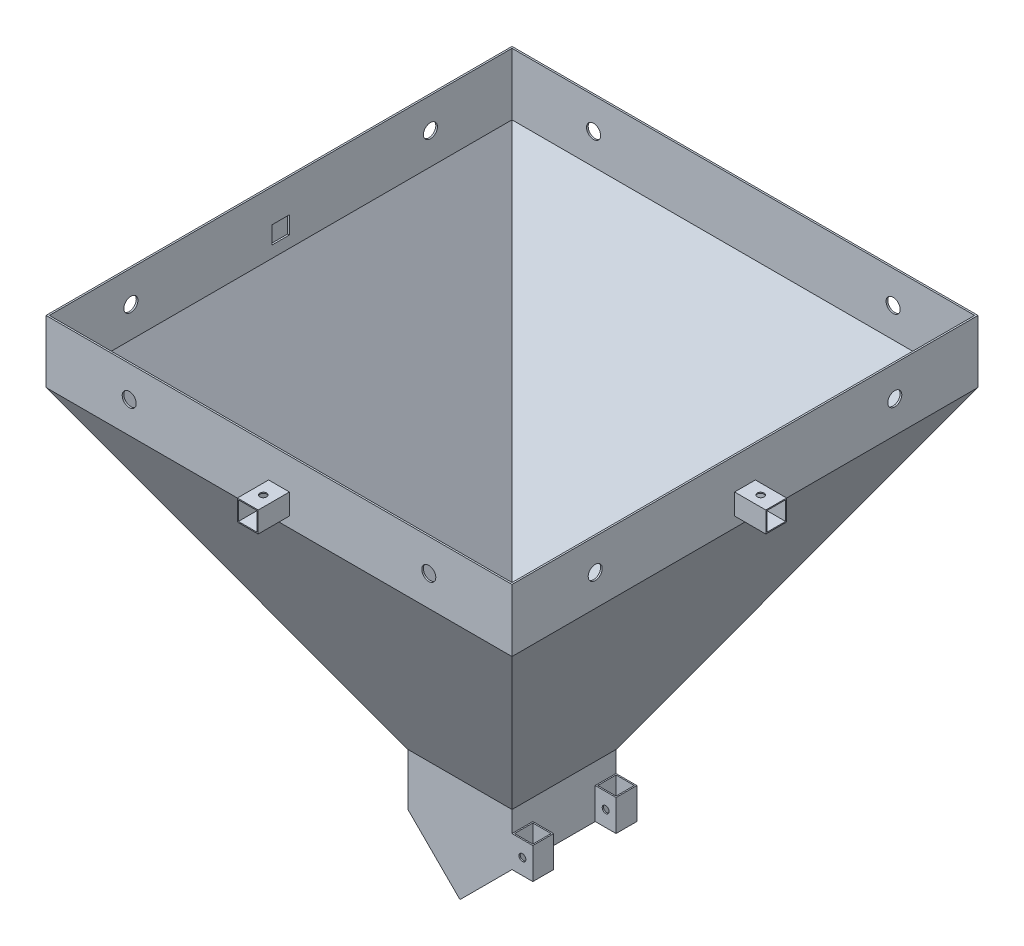
SolidWorks part; units mm, degrees
material "AISI 321 Acero inoxidable recocido (SS)"
ref_plane "Alzado" through (0, 0, 0) normal (0, 0, 1) x (1, 0, 0)
ref_plane "Planta" through (0, 0, 0) normal (0, 1, 0) x (1, 0, 0)
ref_plane "Vista lateral" through (0, 0, 0) normal (1, 0, 0) x (0, 0, -1)
sketch "Croquis2" plane through (0, 0, 0) normal (0, 1, 0) x (1, 0, 0)
  line L1 (0, 0) -> (447.9, 0)
  line L2 (0, 0) -> (0, 447.9)
  line L3 (0, 447.9) -> (447.9, 447.9)
  line L4 (447.9, 0) -> (447.9, 447.9)
  dimension "D1" = 447.9
ref_plane "Plano1" through (0, -301.3, 0) normal (0, 1, 0) x (1, 0, 0)
sketch "Croquis3" plane through (0, -301.3, 0) normal (0, 1, 0) x (1, 0, 0)
  line L0 (223.95, 447.9) -> (223.95, 0) construction
  line L1 (0, 447.9) -> (447.9, 447.9) construction
  line L2 (0, 0) -> (447.9, 0) construction
  line L3 (223.95, 0) -> (447.9, 223.95) construction
  line L4 (447.9, 0) -> (447.9, 447.9) construction
  line L5 (447.9, 223.95) -> (0, 223.95) construction
  line L6 (0, 0) -> (0, 447.9) construction
  line L8 (173.95, 273.95) -> (273.95, 273.95)
  line L9 (173.95, 273.95) -> (173.95, 173.95)
  line L10 (173.95, 173.95) -> (273.95, 173.95)
  line L11 (273.95, 273.95) -> (273.95, 173.95)
  line L12 (173.95, 273.95) -> (273.95, 173.95) construction
  line L13 (173.95, 173.95) -> (273.95, 273.95) construction
  point P12 (223.95, 223.95)
  dimension "D1" = 100
loft "Recubrir1" add profiles "Croquis2", "Croquis3" connector at (0, 0, -447.9) connector at (173.95, -301.3, -273.95)
sketch "Croquis4" plane through (0, -301.3, 0) normal (0, -1, 0) x (1, 0, 0)
  line L1 (173.95, -173.95) -> (273.95, -173.95)
  line L2 (173.95, -173.95) -> (173.95, -273.95)
  line L3 (173.95, -273.95) -> (273.95, -273.95)
  line L4 (273.95, -173.95) -> (273.95, -273.95)
  line L5 (173.95, -173.95) -> (273.95, -273.95) construction
  line L6 (173.95, -273.95) -> (273.95, -173.95) construction
  point P0 (223.95, -223.95)
extrude "Saliente-Extruir1" add sketch "Croquis4" along normal blind 50
sketch "Croquis5" plane through (0, 0, -173.95) normal (0, 0, 1) x (1, 0, 0)
  line L0 (223.95, -351.3) -> (223.95, -515.4339) construction
  line L1 (273.95, -351.3) -> (173.95, -351.3) construction
  line L2 (173.95, -351.3) -> (223.95, -401.3) construction
  line L4 (173.95, -351.3) -> (273.95, -351.3)
  line L5 (173.95, -351.3) -> (223.95, -401.3)
  line L6 (273.95, -351.3) -> (223.95, -401.3)
  dimension "D1" = 45
extrude "Saliente-Extruir2" add sketch "Croquis5" against normal up to surface (100 mm away) up to face at (236.45, -338.8, -273.95)
ref_plane "Plano2" through (0, 0, 0) normal (1, 0, 0) x (0, 0, -1)
ref_plane "Plano3" through (0, 0, 0) normal (0, 0, 1) x (1, 0, 0)
ref_plane "Plano4" through (447.9, 0, 0) normal (1, 0, 0) x (0, 0, -1)
ref_plane "Plano5" through (0, 0, -447.9) normal (0, 0, -1) x (-1, 0, 0)
sketch "Croquis11" plane through (0, 0, 0) normal (0, 1, 0) x (1, 0, 0)
  line L1 (0, 0) -> (447.9, 0)
  line L2 (0, 0) -> (0, 447.9)
  line L3 (0, 447.9) -> (447.9, 447.9)
  line L4 (447.9, 0) -> (447.9, 447.9)
extrude "Saliente-Extruir7" add sketch "Croquis11" along normal blind 60
sketch "Croquis6" plane through (0, 0, 0) normal (1, 0, 0) x (0, 0, -1)
  line L1 (0, 0) -> (223.95, 0) construction
  line L2 (447.9, 0) -> (0, 0) construction
  line L7 (223.95, 0) -> (223.95, 60) construction
  line L8 (447.9, 60) -> (0, 60) construction
  circle A0 centre (373.6075, 30) radius 7
  circle A2 centre (74.2925, 32.5822) radius 7
  dimension "D1" = 14
  dimension "D2" = 30
extrude "Saliente-Extruir3" [suppressed] add sketch "Croquis6" against normal blind 25
sketch "Croquis7" plane through (0, 0, 0) normal (0, 0, 1) x (1, 0, 0)
  line L0 (0, 0) -> (0, -30.0545) construction
  line L1 (0, -228.085) -> (0, 228.085) construction
  line L2 (0, -30.0545) -> (447.9, -30.0545) construction
  line L3 (0, 0) -> (447.9, 0) construction
  line L4 (223.95, -30.0545) -> (223.95, -72.7788) construction
  circle A0 centre (73.95, 30) radius 7
  circle A1 centre (373.95, 30) radius 7
  point P16 (223.95, 0)
  dimension "D1" = 14
  dimension "D2" = 30
  dimension "D3" = 150
extrude "Saliente-Extruir4" [suppressed] add sketch "Croquis7" along normal blind 25
sketch "Croquis12" plane through (-88.675, -88.675, 0) normal (-0.7071, -0.7071, 0) x (0, 0, 1)
  line L5 (-273.95, -442.1185) -> (-173.95, -442.1185) construction
  line L6 (-270.775, -388.9435) -> (-177.125, -388.9435)
  line L7 (-270.775, -388.9435) -> (-270.775, -438.9435)
  line L8 (-270.775, -438.9435) -> (-177.125, -438.9435)
  line L9 (-177.125, -388.9435) -> (-177.125, -438.9435)
  line L10 (-273.95, -442.1185) -> (-273.95, -371.4078) construction
  dimension "D1" = 93.65
  dimension "D2" = 50
  dimension "D3" = 3.175
  dimension "D4" = 3.175
extrude "Cortar-Extruir1" cut sketch "Croquis12" against normal blind 3.175
sketch "Croquis13" plane through (0, 0, 0) normal (-1, 0, 0) x (0, 0, 1)
  line L0 (-223.95, 60) -> (-223.95, -301.3) construction
  line L1 (-447.9, 60) -> (0, 60) construction
  line L2 (-273.95, -301.3) -> (-173.95, -301.3) construction
  line L3 (-447.9, 0) -> (0, 0) construction
  line L4 (-233.95, 30) -> (-213.95, 30)
  line L5 (-233.95, 30) -> (-233.95, 10)
  line L6 (-233.95, 10) -> (-213.95, 10)
  line L7 (-213.95, 30) -> (-213.95, 10)
  line L8 (-233.95, 30) -> (-213.95, 10) construction
  line L9 (-233.95, 10) -> (-213.95, 30) construction
  line L10 (-232.75, 28.8) -> (-215.15, 28.8)
  line L11 (-215.15, 28.8) -> (-215.15, 11.2)
  line L12 (-232.75, 11.2) -> (-215.15, 11.2)
  line L13 (-232.75, 28.8) -> (-232.75, 11.2)
  point P6 (-223.95, 20)
  dimension "D1" = 20
  dimension "D2" = 20
  dimension "D3" = 20
  dimension "D4" = 1.2
extrude "Saliente-Extruir8" add sketch "Croquis13" along normal blind 30 contours L7 L4 L5 L6 L13 L10 L11 L12 | L6 L7 L4 L5 region at (0, 29.7172, -223.95)
shell "Vaciado1" thickness 1.59 removed face at (223.95, 60, -223.95) removed face at (206.2723, -379.1322, -223.95)
ref_plane "Plano6" through (0, -351.3, 0) normal (0, 1, 0) x (0, 0, 1)
sketch "Croquis15" plane through (0, -351.3, 0) normal (0, 1, 0) x (0, 0, 1)
  line L0 (-223.95, 273.95) -> (-223.95, 318.5598) construction
  line L1 (-173.95, 273.95) -> (-193.95, 273.95)
  line L2 (-173.95, 273.95) -> (-173.95, 293.95)
  line L3 (-173.95, 293.95) -> (-193.95, 293.95)
  line L4 (-193.95, 273.95) -> (-193.95, 293.95)
  line L5 (-173.95, 273.95) -> (-273.95, 273.95) construction
  line L6 (-253.95, 273.95) -> (-253.95, 293.95)
  line L7 (-273.95, 293.95) -> (-253.95, 293.95)
  line L8 (-273.95, 273.95) -> (-273.95, 293.95)
  line L9 (-273.95, 273.95) -> (-253.95, 273.95)
  line L10 (-175.15, 275.15) -> (-192.75, 275.15)
  line L11 (-192.75, 275.15) -> (-192.75, 292.75)
  line L12 (-175.15, 292.75) -> (-192.75, 292.75)
  line L13 (-175.15, 275.15) -> (-175.15, 292.75)
  line L14 (-255.15, 275.15) -> (-255.15, 292.75)
  line L15 (-272.75, 292.75) -> (-255.15, 292.75)
  line L16 (-272.75, 275.15) -> (-272.75, 292.75)
  line L17 (-272.75, 275.15) -> (-255.15, 275.15)
  dimension "D3" = 20
  dimension "D4" = 20
  dimension "D1" = 1.2
  dimension "D2" = 1.2
extrude "Saliente-Extruir9" add sketch "Croquis15" along normal blind 30
sketch "Croquis16" plane through (0, 0, 0) normal (0, 0, 1) x (1, 0, 0)
  line L0 (223.95, -301.3) -> (223.95, 60) construction
  line L1 (173.95, -301.3) -> (273.95, -301.3) construction
  line L2 (0, 60) -> (447.9, 60) construction
  line L3 (0, 0) -> (447.9, 0) construction
  line L4 (213.95, 30) -> (233.95, 30)
  line L5 (213.95, 30) -> (213.95, 10)
  line L6 (213.95, 10) -> (233.95, 10)
  line L7 (233.95, 30) -> (233.95, 10)
  line L8 (213.95, 30) -> (233.95, 10) construction
  line L9 (213.95, 10) -> (233.95, 30) construction
  line L10 (214.95, 29) -> (232.95, 29)
  line L11 (232.95, 29) -> (232.95, 11)
  line L12 (214.95, 11) -> (232.95, 11)
  line L13 (214.95, 29) -> (214.95, 11)
  point P6 (223.95, 20)
  dimension "D1" = 10
  dimension "D3" = 20
  dimension "D2" = 1
extrude "Saliente-Extruir10" add sketch "Croquis16" along normal blind 30
sketch "Croquis17" plane through (447.9, 0, 0) normal (1, 0, 0) x (0, 0, -1)
  line L0 (223.95, -301.3) -> (223.95, 60) construction
  line L1 (173.95, -301.3) -> (273.95, -301.3) construction
  line L2 (0, 60) -> (447.9, 60) construction
  line L3 (214.95, 29) -> (232.95, 29)
  line L4 (213.95, 30) -> (233.95, 30)
  line L5 (213.95, 30) -> (213.95, 10)
  line L6 (213.95, 10) -> (233.95, 10)
  line L7 (233.95, 30) -> (233.95, 10)
  line L8 (213.95, 30) -> (233.95, 10) construction
  line L9 (213.95, 10) -> (233.95, 30) construction
  line L10 (232.95, 29) -> (232.95, 11)
  line L11 (214.95, 11) -> (232.95, 11)
  line L12 (214.95, 29) -> (214.95, 11)
  line L13 (0, 0) -> (447.9, 0) construction
  point P6 (223.95, 20)
  point P17 (223.95, 10)
  dimension "D2" = 10
  dimension "D3" = 20
  dimension "D1" = 1
extrude "Saliente-Extruir11" add sketch "Croquis17" along normal blind 30
hole_wizard "Taladro de margen para M121" positions "Croquis18" profile "Croquis19" hole size "M12" standard "Ansi Metric" end condition through all
sketch "Croquis18" plane through (0, 0, 0) normal (0, 0, 1) x (1, 0, 0)
  line L0 (0, 60) -> (0, 0) construction
  line L1 (447.9, 60) -> (447.9, 0) construction
  point P0 (80, 30)
  point P2 (367.9, 29.1845)
  dimension "D1" = 80
  dimension "D2" = 80
  dimension "D3" = 30
sketch "Croquis19" plane through (80, 30, 0) normal (1, 0, 0) x (0, -1, 0)
  line L0 (0, 0) -> (0, 447.9001)
  line L1 (0, 447.9001) -> (6.75, 447.9001)
  line L2 (6.75, 447.9001) -> (6.75, 0)
  line L5 (6.75, 0) -> (0, 0)
  line L11 (0, -6.35) -> (0, 107.95) construction
  dimension "Diámetro de taladro hasta el siguiente" = 13.5
  dimension "Profundidad de taladro hasta el siguiente" = 447.9001
hole_wizard "Taladro de margen para M122" positions "Croquis20" profile "Croquis21" hole size "M12" standard "Ansi Metric" end condition through all
sketch "Croquis20" plane through (447.9, 0, 0) normal (1, 0, 0) x (0, 0, -1)
  point P0 (80, 30)
  point P2 (367.9, 30.6358)
  dimension "D1" = 30
  dimension "D2" = 80
  dimension "D3" = 80
sketch "Croquis21" plane through (447.9, 30, -80) normal (0, 1, 0) x (0, 0, -1)
  line L0 (0, 0) -> (0, 477.9)
  line L1 (0, 477.9) -> (6.75, 477.9)
  line L2 (6.75, 477.9) -> (6.75, 0)
  line L5 (6.75, 0) -> (0, 0)
  line L11 (0, -6.35) -> (0, 107.95) construction
  dimension "Diámetro de taladro hasta el siguiente" = 13.5
  dimension "Profundidad de taladro hasta el siguiente" = 477.9
hole_wizard "Taladro de margen para M61" positions "Croquis22" profile "Croquis23" hole size "M6" standard "Ansi Metric" end condition through all
sketch "Croquis22" plane through (0, 0, -173.95) normal (0, 0, 1) x (1, 0, 0)
  point P0 (283.95, -336.3)
  dimension "D1" = 15
  dimension "D2" = 10
sketch "Croquis23" plane through (283.95, -336.3, -173.95) normal (1, 0, 0) x (0, -1, 0)
  line L0 (0, 0) -> (0, 273.9501)
  line L1 (0, 273.9501) -> (3.3, 273.9501)
  line L2 (3.3, 273.9501) -> (3.3, 0)
  line L5 (3.3, 0) -> (0, 0)
  line L11 (0, -6.35) -> (0, 107.95) construction
  dimension "Diámetro de taladro hasta el siguiente" = 6.6
  dimension "Profundidad de taladro hasta el siguiente" = 273.9501
sketch "Croquis24" plane through (0, 0, -447.9) normal (0, 0, -1) x (-1, 0, 0)
  line L1 (-213.95, 30) -> (-233.95, 30)
  line L2 (-213.95, 30) -> (-213.95, 10)
  line L3 (-213.95, 10) -> (-233.95, 10)
  line L4 (-233.95, 30) -> (-233.95, 10)
  line L5 (-232.95, 11) -> (-214.95, 11)
  line L6 (-232.95, 11) -> (-232.95, 29)
  line L7 (-232.95, 29) -> (-214.95, 29)
  line L8 (-214.95, 11) -> (-214.95, 29)
extrude "Saliente-Extruir12" add sketch "Croquis24" along normal blind 30
sketch "Croquis25" plane through (0, 0, 0) normal (-1, 0, 0) x (0, 0, 1)
  line L0 (-213.95, 30) -> (-213.95, 10) construction
  line L1 (-233.95, 30) -> (-213.95, 30)
  line L2 (-233.95, 30) -> (-233.95, 10)
  line L3 (-233.95, 10) -> (-213.95, 10)
  line L4 (-213.95, 30) -> (-213.95, 10)
  line L5 (-213.95, 10) -> (-233.95, 10) construction
  line L6 (-232.95, 11) -> (-232.95, 29) construction
  line L7 (-214.95, 11) -> (-232.95, 11) construction
  line L8 (-214.95, 11) -> (-214.95, 29) construction
  line L9 (-214.95, 29) -> (-232.95, 29) construction
  line L10 (-232.95, 11) -> (-232.95, 29) construction
  line L11 (-232.95, 29) -> (-214.95, 29) construction
extrude "Saliente-Extruir13" add sketch "Croquis25" along normal blind 30
hole_wizard "Taladro de margen para M62" positions "Croquis26" profile "Croquis27" hole size "M6" standard "Ansi Metric" end condition through all
sketch "Croquis26" plane through (0, 30, 0) normal (0, 1, 0) x (1, 0, 0)
  line L0 (233.95, -30) -> (213.95, -30) construction
  line L1 (477.9, 233.95) -> (477.9, 213.95) construction
  line L2 (213.95, 477.9) -> (233.95, 477.9) construction
  line L3 (-30, 213.95) -> (-30, 233.95) construction
  point P2 (462.9, 223.95)
  point P4 (223.95, 462.9)
  point P6 (-15, 223.95)
  point P8 (223.95, -15)
  dimension "D1" = 15
  dimension "D2" = 15
  dimension "D3" = 15
  dimension "D4" = 15
sketch "Croquis27" plane through (462.9, 30, -223.95) normal (1, 0, 0) x (0, 0, 1)
  line L0 (0, 0) -> (0, 431.3)
  line L1 (0, 431.3) -> (3.3, 431.3)
  line L2 (3.3, 431.3) -> (3.3, 0)
  line L5 (3.3, 0) -> (0, 0)
  line L11 (0, -6.35) -> (0, 107.95) construction
  dimension "Diámetro de taladro hasta el siguiente" = 6.6
  dimension "Profundidad de taladro hasta el siguiente" = 431.3
equation "\"Boca entrada\"= 44.79cm"
equation "\"Boca salida\"= 10cm"
equation "\"Alto prisma\"= 6cm"
equation "\"Alto prisma salida\"= 5cm"
equation "\"Altura\"= ( \"Boca entrada\" - \"Boca salida\" ) / ( tan ( \"Angulo vertical\" ) * \"2A\" )"
equation "\"Angulo vertical\"= 30°"
equation "\"D1@Croquis2\"=\"Boca entrada\""
equation "\"D1@Croquis3\"=\"Boca salida\""
equation "\"D1@Saliente-Extruir7\"=\"Alto prisma\""
equation "\"Espesor\" = 3.175milímetro"
